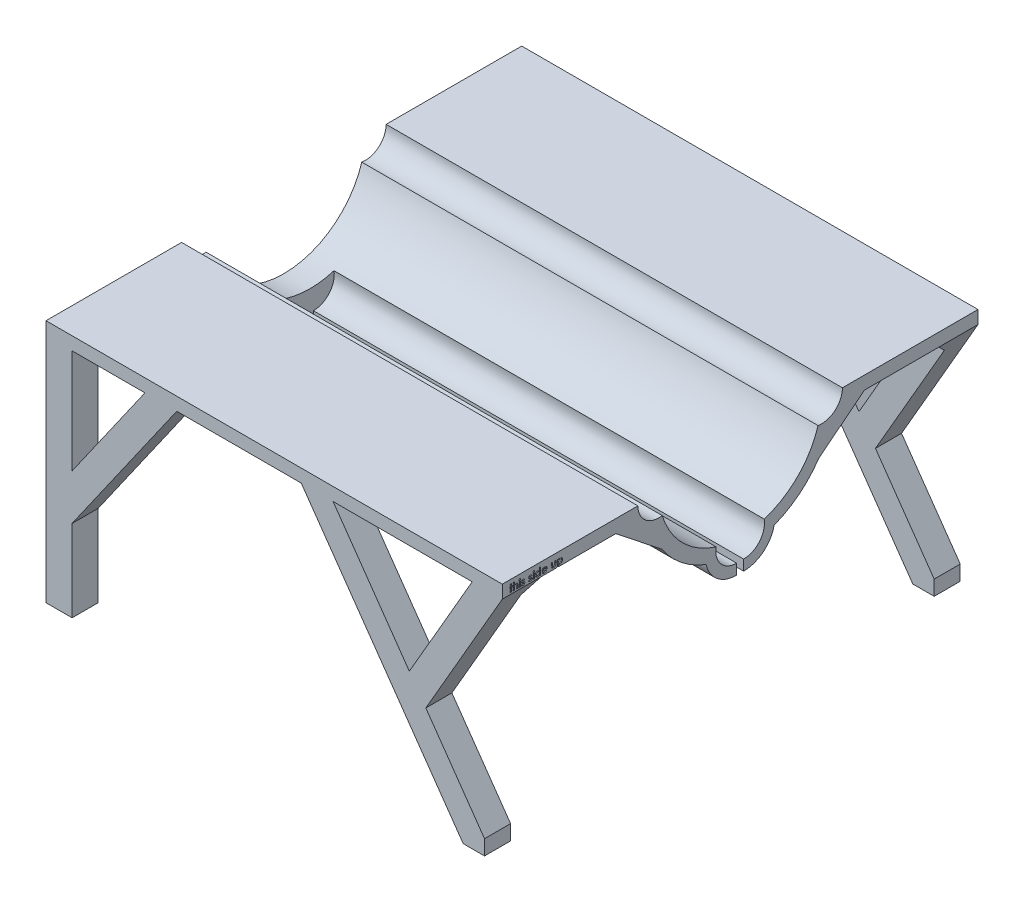
SolidWorks part; units mm, degrees
ref_plane "Front Plane" through (0, 0, 0) normal (0, 0, 1) x (1, 0, 0)
ref_plane "Top Plane" through (0, 0, 0) normal (0, 1, 0) x (1, 0, 0)
ref_plane "Right Plane" through (0, 0, 0) normal (1, 0, 0) x (0, 0, -1)
sketch "Sketch1" plane through (0, 0, 0) normal (1, 0, 0) x (0, 0, -1)
  line L0 (-87.8601, 0) -> (97.8786, 0) construction
  line L1 (-39.6557, -1.5875) -> (-115.8557, -1.5875)
  line L2 (0, -100.4363) -> (0, 110.3288) construction
  line L3 (39.6557, -1.5875) -> (115.8557, -1.5875)
  line L4 (-1.7018, -39.651) -> (-1.7018, -100.4363) construction
  line L5 (1.7018, -39.651) -> (1.7018, -100.4363) construction
  line L6 (-45.3481, -7.9375) -> (-115.8557, -7.9375)
  line L7 (45.3481, -7.9375) -> (115.8557, -7.9375)
  line L8 (-115.8557, -1.5875) -> (-115.8557, -7.9375)
  line L9 (115.8557, -1.5875) -> (115.8557, -7.9375)
  line L11 (-1.9741, -45.9952) -> (-1.7018, -45.9952)
  line L12 (-1.7018, -45.9952) -> (-1.7018, -39.651)
  line L13 (1.9741, -45.9952) -> (1.7018, -45.9952)
  line L14 (1.7018, -45.9952) -> (1.7018, -39.651)
  circle A0 centre (0, 0) radius 39.6875 construction
  arc A1 (-39.6557, -1.5875) -> (-1.7018, -39.651) centre (0, 0) ccw
  arc A2 (39.6557, -1.5875) -> (1.7018, -39.651) centre (0, 0) cw
  arc A3 (-46.0057, -1.5875) -> (-38.895, -7.8918) centre (-39.6557, -1.5875) ccw
  arc A4 (46.0057, -1.5875) -> (38.895, -7.8918) centre (39.6557, -1.5875) cw
  arc A5 (-45.3481, -7.9375) -> (-1.9741, -45.9952) centre (0, 0) ccw
  arc A6 (45.3481, -7.9375) -> (1.9741, -45.9952) centre (0, 0) cw
  dimension "D1" = 79.375
  dimension "D5" = 6.35
  dimension "D8" = 1.9741
  dimension "D2" = 185.7387
  dimension "D3" = 1.5875
  dimension "D4" = 1.7018
  dimension "D6" = 76.2
  dimension "D7" = 6.35
extrude "Boss-Extrude1" add sketch "Sketch1" along normal blind 222.25 contours L6 A5 L11 L12 A1 A3 L1 L8 | A6 L7 L9 L3 A4 A2 L14 L13 region at (0, -7.2555, 44.6809) region at (0, -2.8124, -80.9307)
chamfer "Chamfer1" distance 7.62 angle 45 1 edges at (111.125, -7.9375, 45.3481) first distance on face at (111.125, -7.9375, 80.6019)
chamfer "Chamfer2" distance 7.62 angle 45 1 edges at (111.125, -7.9375, -45.3481) first distance on face at (111.125, -30.7857, -27.0123)
sketch "Sketch2" plane through (0, 0, 0) normal (-1, 0, 0) x (0, 0, 1)
  line L0 (0, -38.0235) -> (0, -120.5735) construction
  line L1 (-152.5028, -120.5735) -> (152.2972, -120.5735) construction
  line L2 (-103.1557, -7.9375) -> (-103.1557, -120.5735)
  line L3 (-115.8557, -7.9375) -> (-103.1557, -7.9375)
  line L4 (-115.8557, -7.9375) -> (-115.8557, -120.5735)
  line L5 (-115.8557, -120.5735) -> (-103.1557, -120.5735)
  line L7 (115.8557, -7.9375) -> (103.1557, -7.9375)
  line L8 (115.8557, -7.9375) -> (115.8557, -120.5735)
  line L9 (115.8557, -120.5735) -> (103.1557, -120.5735)
  line L10 (103.1557, -7.9375) -> (103.1557, -120.5735)
  dimension "D1" = 82.55
  dimension "D2" = 304.8
  dimension "D3" = 152.5028
  dimension "D4" = 12.7
  dimension "D5" = 0
extrude "Boss-Extrude2" add sketch "Sketch2" against normal blind 12.7
sketch "Sketch3" plane through (222.25, 0, 0) normal (1, 0, 0) x (0, 0, -1)
  line L0 (-16.7727, -35.9691) -> (0, 0) construction
  line L1 (0, 0) -> (16.7727, -35.9691) construction
  line L2 (0, 0) -> (-46.0057, 0) construction
  line L3 (-46.0057, 0) -> (-46.0057, -1.5875) construction
  line L4 (-16.7727, -35.9691) -> (-19.4563, -41.7241)
  line L5 (16.7727, -35.9691) -> (19.4563, -41.7241)
  line L6 (0, -46.0375) -> (0, -58.7375) construction
  arc A0 (-16.7727, -35.9691) -> (16.7727, -35.9691) centre (0, 0) ccw
  arc A1 (-38.895, -7.8918) -> (-1.7018, -39.651) centre (0, 0) ccw construction
  arc A2 (-19.4563, -41.7241) -> (19.4563, -41.7241) centre (0, 0) ccw
  spline S0 degree 3 poles (-19.4563, -41.7241) (-13.1274, -51.7966) (-8.4146, -58.658) (0, -58.7375) knots 0 0 0 0 1 1 1 1
  spline S1 degree 3 poles (19.4563, -41.7241) (13.1274, -51.7966) (8.4146, -58.658) (0, -58.7375) knots 0 0 0 0 1 1 1 1
  arc M5 (1.9741, -45.9952) -> (43.1417, -16.0701) centre (0, 0) ccw
  arc M11 (38.895, -7.8918) -> (1.7018, -39.651) centre (0, 0) cw
  line M12 (1.7018, -39.651) -> (1.7018, -45.9952)
  line M13 (1.7018, -45.9952) -> (1.9741, -45.9952)
  dimension "D4" = 12.7
  dimension "D1" = 65
  dimension "D2" = 50
  dimension "D3" = 6.35
extrude "Boss-Extrude3" add sketch "Sketch3" along normal blind 12.7 contours S1 A2 S0 M5 | L4 A2 A0 M13 M12 | L5 M11 M12 M13 M5 region at (222.25, -41.6964, 8.3802) region at (222.25, -50.3525, 0) region at (222.25, -41.465, -10.0587)
chamfer "Chamfer3" distance 19.05 angle 45 2 edges at (222.25, -38.8466, 18.1145) (222.25, -38.8466, -18.1145)
sketch "Sketch4" plane through (0, 0, 115.8557) normal (0, 0, 1) x (1, 0, 0)
  line L0 (0, -120.5735) -> (203.2, -120.5735) construction
  line L1 (0, -120.5735) -> (0, -1.5875) construction
  line L2 (203.2, -120.5735) -> (124.3314, -7.9375)
  line L3 (222.25, -7.9375) -> (12.7, -7.9375) construction
  line L4 (222.25, -7.9375) -> (177.9989, -84.5826)
  line L5 (213.6032, -113.2891) -> (134.7346, -0.6531)
  line L6 (211.2515, -1.5875) -> (167.0004, -78.2326)
  line L7 (203.2, -120.5735) -> (213.6032, -113.2891)
  line L8 (124.3314, -7.9375) -> (134.7346, -0.6531)
  line L9 (222.25, -7.9375) -> (211.2515, -1.5875)
  line L10 (177.9989, -84.5826) -> (167.0004, -78.2326)
  line L11 (133.4002, -1.5875) -> (135.3889, -1.5875)
  line L12 (222.25, -1.5875) -> (0, -1.5875) construction
  line L13 (203.2, -120.5735) -> (213.6032, -120.5735)
  line L14 (213.6032, -120.5735) -> (213.6032, -113.2891)
  line L16 (63.6909, -7.9375) -> (12.7, -80.7601)
  line L17 (0, -7.9375) -> (222.25, -7.9375) construction
  line L18 (12.7, -120.5735) -> (12.7, -7.9375) construction
  line L19 (53.2877, -0.6531) -> (2.2968, -73.4757)
  line L20 (63.6909, -7.9375) -> (53.2877, -0.6531)
  line L21 (12.7, -80.7601) -> (2.2968, -73.4757)
  line M8 (12.7, -7.9375) -> (222.25, -7.9375)
  dimension "D1" = 55
  dimension "D2" = 203.2
  dimension "D3" = 60
  dimension "D5" = 35
  dimension "D6" = 88.9
  dimension "D4" = 12.7
  dimension "D7" = 12.7
extrude "Boss-Extrude4" add sketch "Sketch4" against normal blind 12.7 contours L6 L5 L2 M8 | L5 L6 L2 L4 | L6 L5 L4 M8 | L2 L7 L5 L4 | L13 L14 L7 | L21 L16 L19 M8 region at (31.8324, -42.5597, 115.8557) region at (195.0435, -97.6209, 115.8557) region at (210.1355, -118.1454, 115.8557) region at (177.4834, -72.7755, 115.8557) region at (152.5814, -37.5907, 115.8557) region at (198.1369, -37.416, 115.8557)
chamfer "Chamfer4" distance 6.35 angle 45 4 edges at (214.9177, -7.9375, 103.1557) (132.0833, -7.9375, 103.1557) (55.939, -7.9375, 103.1557) (6.35, -7.9375, 103.1557)
mirror "Mirror3" about plane through (0, 0, 0) normal (0, 0, 1) of "Boss-Extrude4"
chamfer "Chamfer5" distance 6.35 angle 45 4 edges at (6.35, -7.9375, -103.1557) (55.939, -7.9375, -103.1557) (132.0833, -7.9375, -103.1557) (214.9177, -7.9375, -103.1557)
sketch "Sketch5" plane through (0, -1.5875, 0) normal (0, 1, 0) x (1, 0, 0)
  line L0 (234.95, 0) -> (117.475, 0) construction
  line L1 (234.95, -22.3116) -> (234.95, 22.3116) construction
  line L2 (117.475, 0) -> (117.475, 73.3996) construction
  dimension "D1" = 117.475
  dimension "D2" = 73.3996
ref_plane "Plane1" through (117.475, 0, 0) normal (-1, 0, 0) x (0, 0, 1)
mirror "Mirror6" about plane through (117.475, 0, 0) normal (-1, 0, 0) of "Boss-Extrude3"
sketch "Sketch6" plane through (0, 0, 0) normal (0, 1, 0) x (1, 0, 0)
  line L1 (222.25, 115.8557) -> (263.4622, 115.8557)
  line L2 (222.25, 115.8557) -> (222.25, -113.9179)
  line L3 (222.25, -113.9179) -> (263.4622, -113.9179)
  line L4 (263.4622, 115.8557) -> (263.4622, -113.9179)
  dimension "D1" = 229.7736
  dimension "D2" = 41.2122
extrude "Cut-Extrude1" cut sketch "Sketch6" against normal blind 76.2
sketch "Sketch7" plane through (222.25, 0, 0) normal (1, 0, 0) x (0, 0, -1)
  line L0 (0, 0) -> (0, -80.9024) construction
  line L1 (-11.7132, -37.9196) -> (-1.7018, -37.9196)
  line L2 (-1.7018, -37.9196) -> (-1.7018, -49.811)
  line L3 (1.7018, -37.9196) -> (1.7018, -49.811)
  line L4 (11.7132, -37.9196) -> (1.7018, -37.9196)
  arc A0 (-1.7018, -49.811) -> (-11.7132, -37.9196) centre (-1.7018, -39.651) cw
  arc A1 (-38.895, -7.8918) -> (-1.7018, -39.651) centre (0, 0) ccw construction
  arc A2 (3.4448, -49.6604) -> (11.7132, -37.9196) centre (1.7018, -39.651) ccw
  arc A3 (1.7018, -49.811) -> (11.7132, -37.9196) centre (1.7018, -39.651) ccw
  line M10 (-1.7018, -45.9952) -> (-1.7018, -39.651)
  arc M11 (-1.7018, -39.651) -> (-38.895, -7.8918) centre (0, 0) cw
  dimension "D1" = 10.16
extrude "Cut-Extrude2" cut sketch "Sketch7" against normal blind 209.55 contours A0 M10 M11 | L3 A3 L4 region at (222.25, -43.5976, 6.2405) region at (222.25, -43.044, -6.1458)
sketch "Sketch8" plane through (222.25, 0, 0) normal (1, 0, 0) x (0, 0, -1)
  text T0 "<b>this side up</b>"
extrude "Cut-Extrude3" cut sketch "Sketch8" against normal blind 0.5
sketch "Sketch10" plane through (0, -120.5735, 0) normal (0, -1, 0) x (-1, 0, 0)
  text T0 "<b>:3</b>" font "Courier New" height 2.54
extrude "Cut-Extrude4" cut sketch "Sketch10" against normal blind 0.5
sketch "Sketch11" plane through (222.25, 0, 0) normal (1, 0, 0) x (0, 0, -1)
  line L0 (-1.7018, -49.811) -> (1.7018, -49.811) construction
  line L1 (-1.7018, -54.891) -> (-1.7018, -49.811)
  line L2 (1.7018, -54.891) -> (1.7018, -49.811)
  line L3 (-11.7132, -37.9196) -> (-16.7189, -37.054)
  line L4 (11.7132, -37.9196) -> (16.7189, -37.054)
  arc A0 (-11.7132, -37.9196) -> (-1.7018, -49.811) centre (-1.7018, -39.651) ccw
  arc A1 (-11.7132, -37.9196) -> (-1.7018, -49.811) centre (-1.7018, -39.651) ccw construction
  arc A2 (11.7132, -37.9196) -> (1.7018, -49.811) centre (1.7018, -39.651) cw
  arc A3 (1.7018, -49.811) -> (11.7132, -37.9196) centre (1.7018, -39.651) ccw construction
  arc A4 (16.7189, -37.054) -> (1.7018, -54.891) centre (1.7018, -39.651) cw
  arc A5 (-16.7189, -37.054) -> (-1.7018, -54.891) centre (-1.7018, -39.651) ccw
  dimension "D2" = 5.08
  dimension "D1" = 3.4036
  dimension "D3" = 5.08
extrude "Boss-Extrude5" add sketch "Sketch11" against normal up to surface (209.55 mm away)
sketch "Sketch12" plane through (222.25, 0, 0) normal (1, 0, 0) x (0, 0, -1)
  line L0 (-60.5881, -7.9375) -> (-38.257, -25.6096)
  line L1 (-52.9681, -7.9375) -> (-88.5151, -7.9375) construction
  line L2 (-38.257, -25.6096) -> (-41.9573, -18.9483)
  line L3 (-41.9573, -18.9483) -> (-52.9681, -7.9375)
  line L4 (-52.9681, -7.9375) -> (-60.5881, -7.9375)
  line L5 (0, -80.9024) -> (0, 0) construction
  line L8 (60.5881, -7.9375) -> (38.257, -25.6096)
  line L9 (52.9681, -7.9375) -> (60.5881, -7.9375)
  line L10 (60.5881, -7.9375) -> (38.257, -25.6096)
  line L11 (43.1417, -16.0701) -> (37.5337, -26.4008)
  line L12 (43.1417, -16.0701) -> (52.9681, -7.9375)
  line L13 (37.5337, -26.4008) -> (38.257, -25.6096)
  arc A2 (-41.9573, -18.9483) -> (-16.5809, -42.9479) centre (0, 0) ccw construction
  dimension "D1" = 7.62
  dimension "D2" = 7.62
extrude "Boss-Extrude6" add sketch "Sketch12" against normal up to surface (222.25 mm away) contours L3 L4 L0 L2 | L11 L13 L8 L9 L12 region at (222.25, -14.5436, 49.3939) region at (222.25, -14.7323, -48.7923) up to face at (0, -36.3947, -0.1631)
sketch "Sketch13" plane through (222.25, 0, 0) normal (1, 0, 0) x (0, 0, -1)
  line L0 (-46.0057, -1.5875) -> (-39.6557, -1.5875) construction
  line L1 (-39.6557, -1.5875) -> (0, -1.5875) construction
  line L2 (0, -1.5875) -> (73.3996, -1.5875) construction
  line L3 (0, -1.5875) -> (0, 40.5066) construction
  line L4 (-46.0057, -1.5875) -> (-115.8557, -1.5875) construction
  line L5 (-37.9532, -11.6038) -> (-39.6557, -1.5875)
  line L6 (-39.6557, -1.5875) -> (-49.8157, -1.5875)
  line L7 (37.9532, -11.6038) -> (39.6557, -1.5875)
  line L8 (39.6557, -1.5875) -> (49.8157, -1.5875)
  arc A0 (-49.8157, -1.5875) -> (-37.9532, -11.6038) centre (-39.6557, -1.5875) ccw
  arc A1 (-38.895, -7.8918) -> (-11.7132, -37.9196) centre (0, 0) ccw construction
  arc A2 (49.8157, -1.5875) -> (37.9532, -11.6038) centre (39.6557, -1.5875) cw
  dimension "D1" = 10.16
extrude "Cut-Extrude5" cut sketch "Sketch13" against normal blind 254
